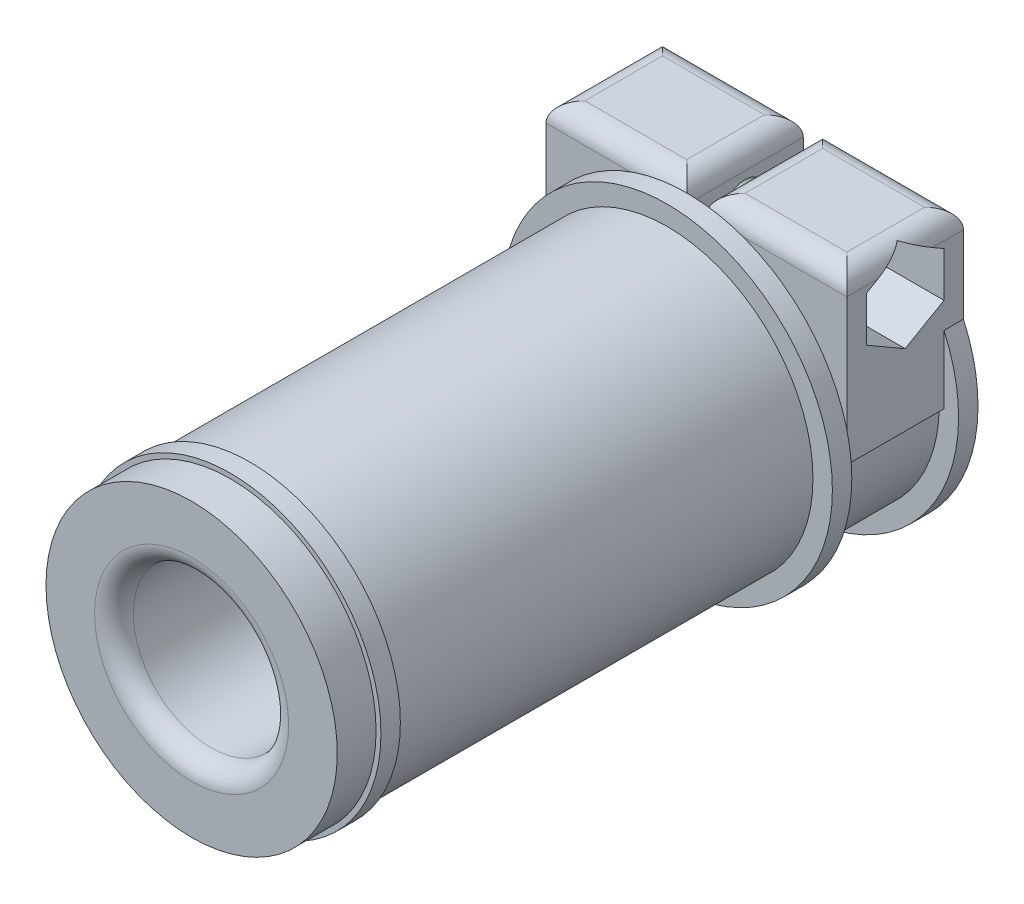
SolidWorks part; units mm, degrees
material "PBT General Purpose"
ref_plane "Front Plane" through (0, 0, 0) normal (0, 0, 1) x (1, 0, 0)
ref_plane "Top Plane" through (0, 0, 0) normal (0, 1, 0) x (1, 0, 0)
ref_plane "Right Plane" through (0, 0, 0) normal (1, 0, 0) x (0, 0, -1)
sketch "Sketch1" plane through (0, 0, 0) normal (0, 0, 1) x (1, 0, 0)
  circle A0 centre (0, 0) radius 4
  circle A1 centre (0, 0) radius 7.5
  dimension "D1" = 8
  dimension "D2" = 15
extrude "Boss-Extrude1" add sketch "Sketch1" along normal blind 32
ref_plane "Plane1" through (0, 0, 0) normal (1, 0, 0) x (0, 0, -1)
ref_plane "Plane2" through (0, 0, 29) normal (0, 0, 1) x (1, 0, 0)
ref_plane "Plane3" through (0, 0, 0) normal (0, 1, 0) x (-1, 0, 0)
sketch "Sketch4" plane through (0, 0, 29) normal (0, 0, 1) x (1, 0, 0)
  circle A0 centre (0, 0) radius 7.75
  circle A1 centre (0, 0) radius 7.5 construction
  circle A2 centre (0, 0) radius 4
  circle A3 centre (0, 0) radius 4 construction
  dimension "D1" = 0.25
ref_axis "Axis1" through (0, 0, 32) along (0, 0, -1)
sketch "Sketch6" plane through (0, 0, 0) normal (0, 1, 0) x (-1, 0, 0)
  line L1 (7.5, 1) -> (8.5, 1)
  line L2 (7.5, 1) -> (7.5, 0)
  line L3 (7.5, 0) -> (8.5, 0)
  line L4 (8.5, 1) -> (8.5, 0)
  dimension "D1" = 1
  dimension "D2" = 1
revolve "Revolve1" add sketch "Sketch6" angle 360 about axis through (0, 0, 32) along (0, 0, -1)
sketch "Sketch7" plane through (0, 0, 0) normal (1, 0, 0) x (0, 0, -1)
  line L0 (-1, 7.5) -> (-32, 7.5) construction
  line L1 (-6.5, 7.5) -> (-7.5, 7.5)
  line L2 (-6.5, 7.5) -> (-6.5, 8.5)
  line L3 (-6.5, 8.5) -> (-7.5, 8.5)
  line L4 (-7.5, 7.5) -> (-7.5, 8.5)
  line L6 (-1, 8.5) -> (-1, -8.5) construction
  dimension "D1" = 1
  dimension "D2" = 1
  dimension "D3" = 5.5
revolve "Revolve2" add sketch "Sketch7" angle 360 about axis through (0, 0, 32) along (0, 0, -1)
sketch "Sketch9" plane through (0, 0, 0) normal (0, 1, 0) x (-1, 0, 0)
  line L0 (0, 0) -> (-0.5, 0)
  line L1 (-7.5, 0) -> (7.5, 0) construction
  line L2 (-0.5, 0) -> (-0.5, 6.5)
  line L3 (-7.5, 6.5) -> (7.5, 6.5) construction
  line L4 (-0.5, 6.5) -> (0.5, 6.5)
  line L5 (-8.5, 6.5) -> (8.5, 6.5) construction
  line L6 (0.5, 6.5) -> (0.5, 0)
  line L7 (0.5, 0) -> (0, 0)
  dimension "D1" = 1
extrude "Cut-Extrude1" cut sketch "Sketch9" along normal through all
sketch "Sketch12" plane through (0, 0, 6.5) normal (0, 0, -1) x (-1, 0, 0)
  line L0 (0, 0) -> (0, 9.5109) construction
  line L1 (4, 0) -> (7.75, 0)
  line L2 (0.5, 3.9686) -> (0.5, 8.4853)
  line L3 (0.5, 8.4853) -> (7.75, 8.4853)
  line L4 (7.75, 0) -> (7.75, 8.4853)
  line L5 (0, 9.3652) -> (0, -9.3652) construction
  line L6 (-7.75, 0) -> (-7.75, 8.4853)
  line L7 (-0.5, 8.4853) -> (-7.75, 8.4853)
  line L8 (-0.5, 3.9686) -> (-0.5, 8.4853)
  line L9 (-4, 0) -> (-7.75, 0)
  arc A0 (-0.5, 3.9686) -> (0.5, 3.9686) centre (0, 0) ccw construction
  arc A1 (-0.5, 3.9686) -> (-4, 0) centre (0, 0) ccw
  arc A2 (4, 0) -> (0.5, 3.9686) centre (0, 0) ccw
  circle A4 centre (0, 0) radius 8.5 construction
  arc A5 (-0.5, 8.4853) -> (0.5, 8.4853) centre (0, 0) ccw construction
  circle A6 centre (0, 0) radius 7.75 construction
extrude "Boss-Extrude3" add sketch "Sketch12" along normal up to surface (6.5 mm away) up to face at (0, -0.0115, 0)
sketch "Sketch15" plane through (0, 0, 6.5) normal (0, 0, -1) x (-1, 0, 0)
  line L0 (0.5, 8.4853) -> (7.75, 8.4853) construction
  line L1 (-7.75, -4) -> (7.75, -4)
  line L2 (-7.75, -4) -> (-7.75, 8.4853)
  line L3 (-7.75, 8.4853) -> (7.75, 8.4853)
  line L4 (7.75, -4) -> (7.75, 8.4853)
  line L5 (-7.75, 3.4911) -> (-7.75, 8.4853) construction
  line L6 (0, 0) -> (0, -4) construction
  arc A3 (-0.5, 3.9686) -> (0.5, 3.9686) centre (0, 0) ccw construction
extrude "Cut-Extrude2" cut sketch "Sketch15" along normal blind 0.5
hole_wizard "CBORE for M2 SHCS1" positions "3DSketch1" profile "Sketch13" counterbore size "M2" standard "Ansi Metric" end condition through all
sketch3d "3DSketch1"
  line L0 (-7.75, 5.9882, 3) -> (-7.75, 8.4853, 3) construction
  line L1 (-7.75, 8.4853, 0) -> (-7.75, 8.4853, 6) construction
  line L3 (-7.75, 5.9882, 3) -> (-7.75, 5.9882, 0) construction
  line L4 (-7.75, 8.4853, 0) -> (-7.75, 3.4911, 0) construction
  point P0 (-7.75, 5.9882, 3)
sketch "Sketch13" plane through (-7.75, 5.9882, 3) normal (0, 1, 0) x (0, 0, 1)
  line L0 (0, 0) -> (0, 16.25)
  line L1 (0, 16.25) -> (1.1, 16.25)
  line L3 (1.1, 16.25) -> (1.1, 4)
  line L4 (1.1, 4) -> (2.2, 4)
  line L5 (2.2, 4) -> (2.2, 0)
  line L7 (2.2, 0) -> (0, 0)
  line L11 (0, -6.35) -> (0, 107.95) construction
  dimension "Thru Hole Dia." = 2.2
  dimension "Thru Hole Depth" = 16.25
  dimension "C'Bore Dia." = 4.4
  dimension "C'Bore Depth" = 4
ref_plane "Plane5" through (4, 0, 0) normal (-1, 0, 0) x (0, 0, 1)
ref_plane "Plane6" through (7.5, 0, 0) normal (1, 0, 0) x (0, 0, -1)
fillet "Fillet4" radius 0.5 2 edges at (6.3443, -4, 6.25) (-6.3443, -4, 6.25)
extrude "Boss-Extrude4" add sketch "Sketch4" along normal blind 1
sketch "Sketch16" plane through (7.75, 0, 0) normal (1, 0, 0) x (0, 0, -1)
  line L0 (-3, 5.9882) -> (-3, 8.2976) construction
  line L1 (-3, 8.2976) -> (-5, 7.1429)
  line L2 (-5, 7.1429) -> (-5, 4.8335)
  line L3 (-5, 4.8335) -> (-3, 3.6788)
  line L4 (-3, 3.6788) -> (-1, 4.8335)
  line L5 (-1, 4.8335) -> (-1, 7.1429)
  line L6 (-1, 7.1429) -> (-3, 8.2976)
  circle A0 centre (-3, 5.9882) radius 2.3094 construction
  dimension "D1" = 4
extrude "Cut-Extrude3" cut sketch "Sketch16" against normal blind 4
fillet "Fillet5" radius 1 10 edges at (0.5, 8.4853, 3) (4.125, 8.4853, 0) (7.75, 8.4853, 3) (4.125, 8.4853, 6) (-7.75, 8.4853, 3) (-4.125, 8.4853, 0) (-0.5, 8.4853, 3) (-4.125, 8.4853, 6) (4, 0, 32) (0, -4, 0)
